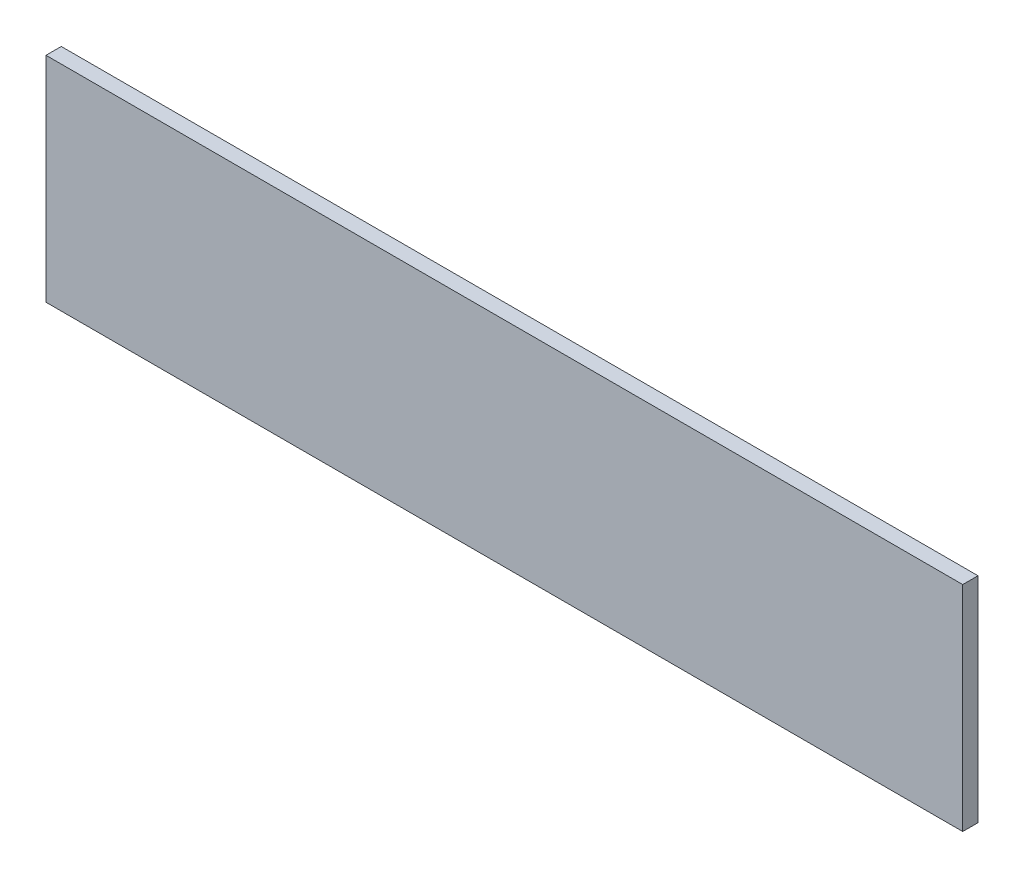
SolidWorks part; units mm, degrees
ref_plane "Plan de face" through (0, 0, 0) normal (0, 0, 1) x (1, 0, 0)
ref_plane "Plan de dessus" through (0, 0, 0) normal (0, 1, 0) x (1, 0, 0)
ref_plane "Plan de droite" through (0, 0, 0) normal (1, 0, 0) x (0, 0, -1)
sketch "Esquisse1" plane through (0, 0, 0) normal (0, 0, 1) x (1, 0, 0)
  line L1 (0, 0) -> (600, 0)
  line L2 (0, 0) -> (0, 140)
  line L3 (0, 140) -> (600, 140)
  line L4 (600, 0) -> (600, 140)
  dimension "D1" = 140
  dimension "D2" = 600
extrude "Boss.-Extru.1" add sketch "Esquisse1" along normal blind 10
